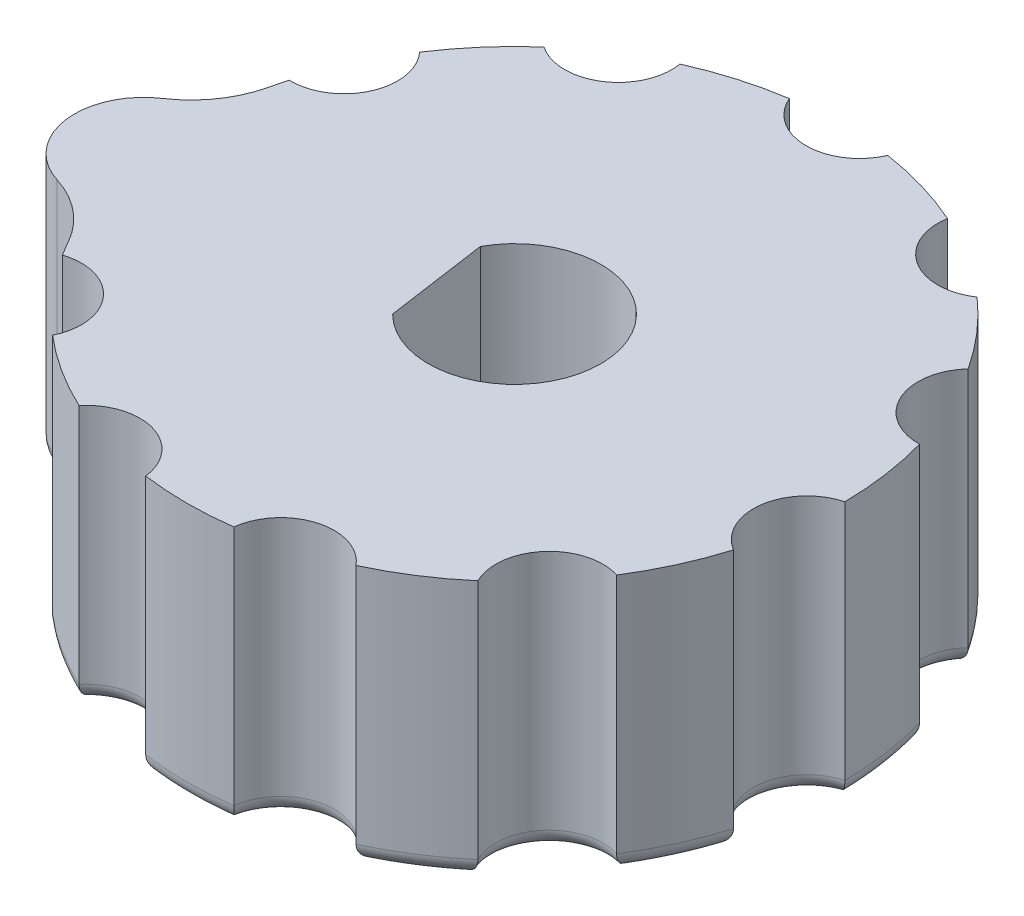
SolidWorks part; units mm, degrees
ref_plane "Front Plane" through (0, 0, 0) normal (0, 0, 1) x (1, 0, 0)
ref_plane "Top Plane" through (0, 0, 0) normal (0, 1, 0) x (1, 0, 0)
ref_plane "Right Plane" through (0, 0, 0) normal (1, 0, 0) x (0, 0, -1)
sketch "Sketch1" plane through (0, 0, 0) normal (0, 1, 0) x (1, 0, 0)
  line L0 (0, 10) -> (0, 9.5) construction
  circle A0 centre (0, 0) radius 9.5
  circle A1 centre (0, 0) radius 2.5
  circle A2 centre (0, 10) radius 1.55
  dimension "D1" = 19
  dimension "D2" = 5
  dimension "D3" = 3.1
  dimension "D4" = 0.5
extrude "Boss-Extrude1" add sketch "Sketch1" along normal blind 7.5 contours A2 A0 A1 | A0 A2 region at (-6.0182, 0, 7.0009) region at (0, 0, -9.0447)
extrude "Boss-Extrude2" add sketch "Sketch1<3>" along normal blind 2 contours A1
sketch "Sketch1<3>" plane through (0, 0, 0) normal (0, 1, 0) x (1, 0, 0) same geometry as "Sketch1"
ref_axis "Axis1" through (0, 0, 0) along (0, 1, 0)
extrude "Cut-Extrude1" cut sketch "Sketch1<4>" along normal through all contours A2
sketch "Sketch1<4>" plane through (0, 0, 0) normal (0, 1, 0) x (1, 0, 0) same geometry as "Sketch1"
pattern_circular "CirPattern1" count 11 over 360 about axis through (0, 0, 0) along (0, 1, 0) skipping 3 of "Cut-Extrude1"
sketch "Sketch2" plane through (0, 7.5, 0) normal (0, 1, 0) x (1, 0, 0)
  line L0 (-2.1931, 1.2001) -> (-1.7662, -1.7694)
  line L1 (0, 0) -> (-9.4033, -1.352) construction
  circle A0 centre (0, 0) radius 2.5 construction
  arc A1 (-9.136, 2.6047) -> (-8.0321, -5.073) centre (0, 0) ccw construction
  circle A2 centre (-9.4033, -1.352) radius 2
  arc A3 (-2.1931, 1.2001) -> (-1.7662, -1.7694) centre (0, 0) ccw
  circle M23 centre (0, 0) radius 2.5
  dimension "D1" = 4
  dimension "D2" = 2
extrude "Boss-Extrude3" add sketch "Sketch2" against normal up to surface (7.5 mm away) contours L1 L0 A3 | L0 L1 M23 | A2 region at (-2.2606, 7.5, -0.2517) region at (-2.0982, 7.5, 0.8784) up to face at (0.8503, 0, -0.1223)
fillet "Fillet2" radius 3 2 edges at (-9.478, 3.75, -0.6466) (-8.9119, 3.75, 3.2907)
fillet "Fillet1" radius 0.5 24 edges at (-9.1998, 0, -2.3692) (-8.1597, 0, 4.8651) (-7.1796, 0, -6.2212) (-2.6765, 0, -9.1152) (2.6765, 0, -9.1152) (7.1796, 0, -6.2212) (9.4033, 0, -1.352) (8.6415, 0, 3.9464) (5.1361, 0, 7.9919) (0, 0, 9.5) (-5.1361, 0, 7.9919) (-6.3861, 0, 5.5336) (-2.3806, 0, 8.1077) (2.3806, 0, 8.1077) (6.3861, 0, 5.5336) (0, 0, -8.45) (-4.5684, 0, -7.1086) (-7.6864, 0, -3.5103) (8.364, 0, 1.2026) (7.6864, 0, -3.5103) (4.5684, 0, -7.1086) (-11.3829, 0, 1.6366) (-9.712, 0, -1.1014) (-9.0083, 0, 3.793)
